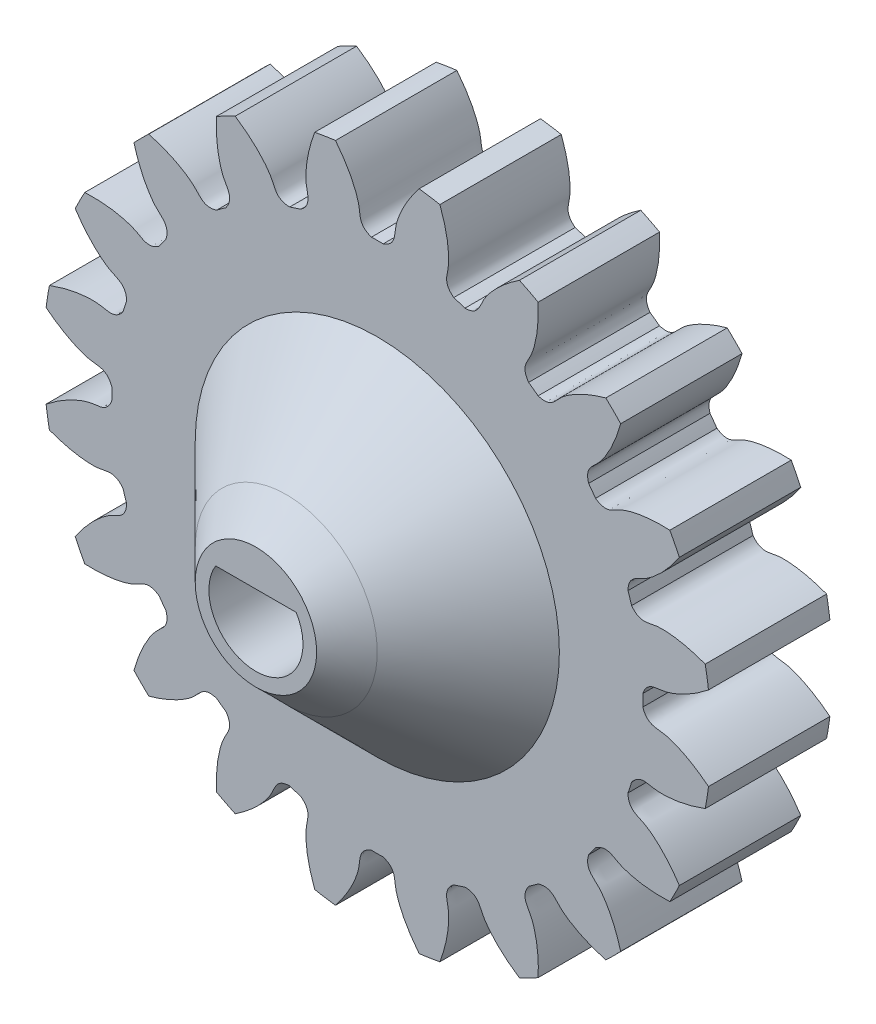
SolidWorks part; units mm, degrees
ref_plane "前视基准面" through (0, 0, 0) normal (0, 0, 1) x (1, 0, 0)
ref_plane "上视基准面" through (0, 0, 0) normal (0, 1, 0) x (1, 0, 0)
ref_plane "右视基准面" through (0, 0, 0) normal (1, 0, 0) x (0, 0, -1)
sketch "草图1" plane through (0, 0, 0) normal (0, 0, 1) x (1, 0, 0)
  circle A0 centre (0, 0) radius 11
extrude "凸台-拉伸1" add sketch "草图1" along normal blind 5
ref_axis "基准轴1" through (0, 0, -0.25) along (0, 0, 1)
sketch "草图2" plane through (0, 0, 0) normal (0, 0, 1) x (1, 0, 0)
  line L0 (0, 0) -> (0, 11) construction
  circle A0 centre (0, 0) radius 11 construction
  arc A1 (0.1933, 8.7479) -> (-0.1933, 8.7479) centre (0, 0) ccw
  arc A2 (3.1812, 12.4983) -> (-3.1812, 12.4983) centre (0, 0) ccw
  spline S0 degree 3 poles (0.1933, 8.7479) (0.6112, 8.8935) (0.5571, 9.1871) (0.6129, 9.47) (0.6189, 9.4976) (0.6263, 9.5286) (0.6353, 9.5632) (0.646, 9.6012) (0.6585, 9.6426) (0.673, 9.6873) (0.6897, 9.7352) (0.7086, 9.7863) (0.7299, 9.8406) (0.7537, 9.8978) (0.7801, 9.958) (0.8094, 10.0211) (0.8415, 10.087) (0.8767, 10.1556) (0.915, 10.2267) (0.9566, 10.3004) (1.0015, 10.3764) (1.05, 10.4548) (1.102, 10.5352) (1.1578, 10.6178) (1.2173, 10.7023) (1.2808, 10.7886) (1.3482, 10.8766) (1.4198, 10.9662) (1.4955, 11.0572) (1.5755, 11.1496) (1.6598, 11.2431) (1.7486, 11.3376) (1.8418, 11.4331) (1.9397, 11.5293) (2.0421, 11.6261) (2.1493, 11.7233) (2.2612, 11.8209) (2.378, 11.9186) (2.4996, 12.0163) (2.6261, 12.1139) (2.7575, 12.2112) (2.9415, 12.3416) (3.0839, 12.4363) (3.1812, 12.4983) knots 0 0 0 0 0.165916 0.170906 0.176664 0.183189 0.190482 0.198542 0.207371 0.216967 0.22733 0.238462 0.250361 0.263027 0.276462 0.290664 0.305634 0.321371 0.337876 0.355149 0.37319 0.391998 0.411574 0.431917 0.453028 0.474907 0.497554 0.520968 0.54515 0.570099 0.595817 0.622302 0.649554 0.677575 0.706363 0.735918 0.766242 0.797333 0.829191 0.861818 0.895212 0.929373 1 1 1 1
  spline S1 degree 3 poles (-0.1933, 8.7479) (-0.6112, 8.8935) (-0.5571, 9.1871) (-0.6129, 9.47) (-0.6189, 9.4976) (-0.6263, 9.5286) (-0.6353, 9.5632) (-0.646, 9.6012) (-0.6585, 9.6426) (-0.673, 9.6873) (-0.6897, 9.7352) (-0.7086, 9.7863) (-0.7299, 9.8406) (-0.7537, 9.8978) (-0.7801, 9.958) (-0.8094, 10.0211) (-0.8415, 10.087) (-0.8767, 10.1556) (-0.915, 10.2267) (-0.9566, 10.3004) (-1.0015, 10.3764) (-1.05, 10.4548) (-1.102, 10.5352) (-1.1578, 10.6178) (-1.2173, 10.7023) (-1.2808, 10.7886) (-1.3482, 10.8766) (-1.4198, 10.9662) (-1.4955, 11.0572) (-1.5755, 11.1496) (-1.6598, 11.2431) (-1.7486, 11.3376) (-1.8418, 11.4331) (-1.9397, 11.5293) (-2.0421, 11.6261) (-2.1493, 11.7233) (-2.2612, 11.8209) (-2.378, 11.9186) (-2.4996, 12.0163) (-2.6261, 12.1139) (-2.7575, 12.2112) (-2.9415, 12.3416) (-3.0839, 12.4363) (-3.1812, 12.4983) knots 0 0 0 0 0.165916 0.170906 0.176664 0.183189 0.190482 0.198542 0.207371 0.216967 0.22733 0.238462 0.250361 0.263027 0.276462 0.290664 0.305634 0.321371 0.337876 0.355149 0.37319 0.391998 0.411574 0.431917 0.453028 0.474907 0.497554 0.520968 0.54515 0.570099 0.595817 0.622302 0.649554 0.677575 0.706363 0.735918 0.766242 0.797333 0.829191 0.861818 0.895212 0.929373 1 1 1 1
extrude "切除-拉伸1" cut sketch "草图2" along normal through all
pattern_circular "阵列(圆周)1" count 20 every 18 about axis through (0, 0, -0.25) along (0, 0, 1) of "切除-拉伸1"
sketch "草图3" plane through (0, 0, 0) normal (0, 0, 1) x (1, 0, 0)
  circle A0 centre (0, 0) radius 10 construction
  dimension "Dn" = 20
sketch "草图4" plane through (0, 0, 5) normal (0, 0, 1) x (1, 0, 0)
  line L0 (-1.3276, 0.8) -> (1.3276, 0.8)
  arc A0 (-1.3276, 0.8) -> (1.3276, 0.8) centre (0, 0) ccw
  dimension "D1" = 3.1
  dimension "D2" = 0.8
extrude "切除-拉伸2" cut sketch "草图4" against normal blind 10
sketch "草图5" plane through (0, 0, 5) normal (0, 0, 1) x (1, 0, 0)
  line L1 (-21.9695, 16.4976) -> (27.0414, 16.4976)
  line L2 (-21.9695, 16.4976) -> (-21.9695, -18.3925)
  line L3 (-21.9695, -18.3925) -> (27.0414, -18.3925)
  line L4 (27.0414, 16.4976) -> (27.0414, -18.3925)
extrude "切除-拉伸3" cut sketch "草图5" against normal blind 1
sketch "草图6" plane through (0, 0, 0) normal (0, 0, -1) x (-1, 0, 0)
  circle A0 centre (0, 0) radius 3
  circle A1 centre (0, 0) radius 7.5
  dimension "D1" = 6
  dimension "D2" = 15
extrude "切除-拉伸4" cut sketch "草图6" against normal blind 1
chamfer "倒角1" [suppressed] distance 1 angle 45
chamfer "倒角2" distance 1 angle 45 1 edges at (-3, 0, 1)
sketch "草图7" plane through (0, 0, 4) normal (0, 0, 1) x (1, 0, 0)
  circle A0 centre (0, 0) radius 3
  dimension "D1" = 6
extrude "凸台-拉伸2" add sketch "草图7" along normal blind 4
chamfer "倒角3" distance 3 angle 45 1 edges at (3, 0, 4)
sketch "草图8" plane through (0, 0, 4) normal (0, 0, -1) x (-1, 0, 0)
  line L1 (1.3276, 0.8) -> (-1.3276, 0.8)
  line L2 (1.3276, 0.8) -> (-1.3276, 0.8)
  arc A1 (-1.3276, 0.8) -> (1.3276, 0.8) centre (0, 0) ccw
  arc A2 (-1.3276, 0.8) -> (1.3276, 0.8) centre (0, 0) ccw
  dimension "D1" = 0
extrude "切除-拉伸5" cut sketch "草图8" against normal blind 8
chamfer "倒角4" distance 1 angle 45 1 edges at (3, 0, 8)
